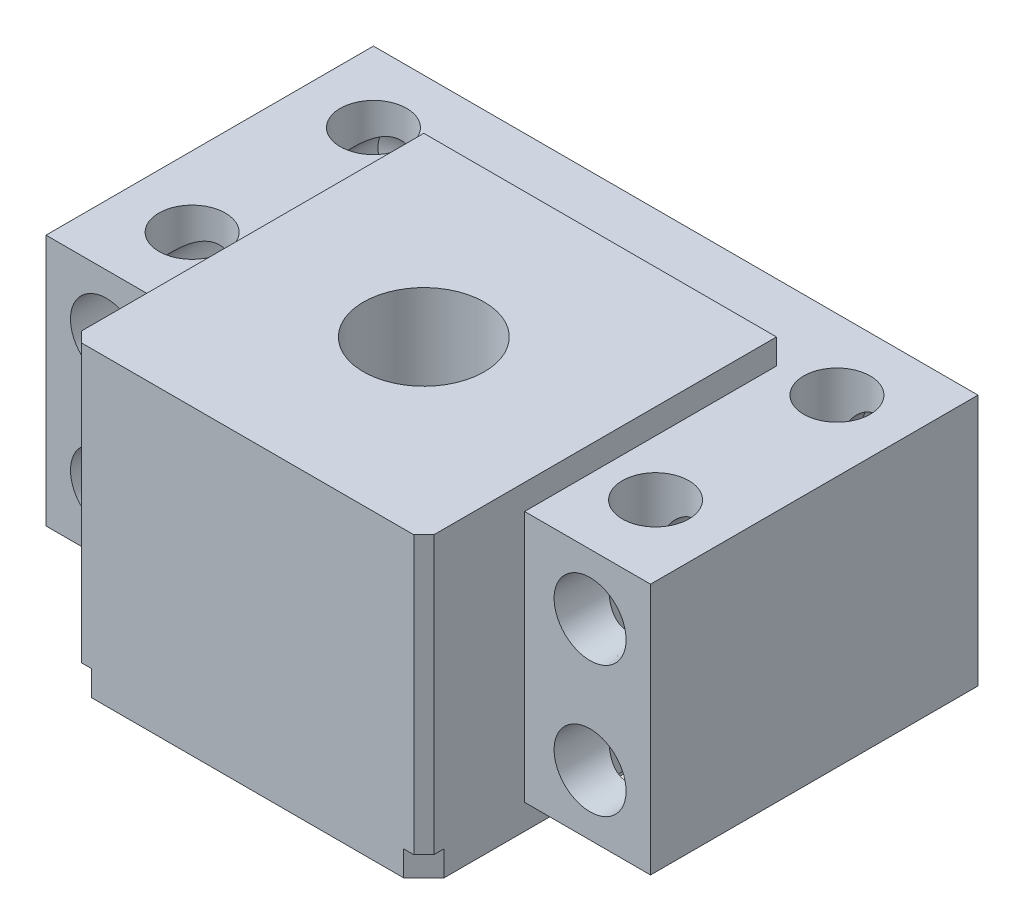
SolidWorks part; units mm, degrees
ref_plane "정면" through (0, 0, 0) normal (0, 0, 1) x (1, 0, 0)
ref_plane "윗면" through (0, 0, 0) normal (0, 1, 0) x (1, 0, 0)
ref_plane "우측면" through (0, 0, 0) normal (1, 0, 0) x (0, 0, -1)
sketch "스케치1" plane through (0, 0, 0) normal (0, 0, 1) x (1, 0, 0)
  line L1 (-30, 12.5) -> (30, 12.5)
  line L2 (-30, 12.5) -> (-30, -12.5)
  line L3 (-30, -12.5) -> (30, -12.5)
  line L4 (30, 12.5) -> (30, -12.5)
  line L5 (-30, 12.5) -> (30, -12.5) construction
  line L6 (-30, -12.5) -> (30, 12.5) construction
  point P0 (0, 0)
  dimension "D1" = 60
  dimension "D2" = 25
extrude "보스-돌출1" add sketch "스케치1" along normal blind 32.5
sketch "스케치2" plane through (0, -12.5, 0) normal (0, -1, 0) x (1, 0, 0)
  line L0 (-30, 0) -> (30, 0) construction
  circle A0 centre (-23, 25) radius 3.3002
  circle A1 centre (-23, 7) radius 3.3
  circle A2 centre (23, 25) radius 3.3002
  circle A3 centre (23, 7) radius 3.3002
  dimension "D1" = 6.6005
  dimension "D2" = 6.6
  dimension "D7" = 6.6005
  dimension "D8" = 6.6005
  dimension "D3" = 18
  dimension "D4" = 25
  dimension "D5" = 25
  dimension "D6" = 18
  dimension "D9" = 23
  dimension "D10" = 0
  dimension "D11" = 46
  dimension "D12" = 46
extrude "컷-돌출1" cut sketch "스케치2" against normal through all contours A1 | A3 | A2 | A0 region at (-23, -12.5, 7) region at (23, -12.5, 25) region at (23, -12.5, 7)
hole_wizard "1/16 Rc 나사 구멍1" positions "스케치3" profile "스케치4" size "1/16" standard "ISO"
sketch "스케치3" plane through (0, 0, 32.5) normal (0, 0, 1) x (1, 0, 0)
  line L0 (30, 12.5) -> (-30, 12.5) construction
  line L1 (-30, 12.5) -> (-30, -12.5) construction
  line L2 (-30, -12.5) -> (30, -12.5) construction
  line L3 (30, -12.5) -> (30, 12.5) construction
  point P0 (-24, 6.5)
  point P2 (-24, -6.5)
  point P4 (24, 6.5)
  point P6 (24, -6.5)
  dimension "D1" = 6
  dimension "D2" = 6
  dimension "D3" = 6
  dimension "D4" = 6
  dimension "D5" = 6
  dimension "D6" = 6
  dimension "D7" = 6
  dimension "D8" = 6
sketch "스케치4" plane through (-24, 6.5, 32.5) normal (1, 0, 0) x (0, -1, 0)
  line L0 (0, 0) -> (0, 31.8326)
  line L1 (3.05, 30) -> (0, 31.8326)
  line L2 (-3.05, 30) -> (0, 31.8326) construction
  line L3 (3.05, 30) -> (3.05, 7.4)
  line L4 (3.05, 7.4) -> (3.34, 7.4)
  line L5 (3.34, 7.4) -> (3.571, 0)
  line L6 (-3.34, 7.4) -> (-3.571, 0) construction
  line L7 (3.571, 0) -> (0, 0)
  line L8 (0, -6.35) -> (0, 107.95) construction
  line L11 (-3.05, 7.4) -> (-3.34, 7.4) construction
  dimension "탭 드릴 지름" = 6.1
  dimension "탭 드릴 깊이" = 30
  dimension "나사산 지름" = 7.142
  dimension "나사산 각도" = 3.576
  dimension "나사산 깊이" = 7.4
  dimension "드릴 각도" = 118
cosmetic thread "구멍 나사산1" parameters "D1"=7.4, "D2"=7.723
cosmetic thread "구멍 나사산2" parameters "D1"=7.4, "D2"=7.723
cosmetic thread "구멍 나사산3" parameters "D1"=7.4, "D2"=7.723
cosmetic thread "구멍 나사산4" parameters "D1"=7.4, "D2"=7.723
sketch "스케치5" plane through (0, -12.5, 0) normal (0, -1, 0) x (1, 0, 0)
  line L0 (-30, 0) -> (30, 0) construction
  line L1 (-17.5, 42.5) -> (17.5, 42.5)
  line L2 (-17.5, 42.5) -> (-17.5, 7.5)
  line L3 (-17.5, 7.5) -> (17.5, 7.5)
  line L4 (17.5, 42.5) -> (17.5, 7.5)
  line L5 (-17.5, 42.5) -> (17.5, 7.5) construction
  line L6 (-17.5, 7.5) -> (17.5, 42.5) construction
  point P0 (0, 25)
  dimension "D1" = 25
  dimension "D2" = 35
  dimension "D3" = 35
extrude "보스-돌출2" add sketch "스케치5" against normal blind 27.5
chamfer "모따기1" distance 1 angle 45 2 edges at (17.5, 1.25, 42.5) (-17.5, 1.25, 42.5)
extrude "보스-돌출3" add sketch "스케치5<2>" along normal blind 2.5
sketch "스케치5<2>" plane through (0, -12.5, 0) normal (0, -1, 0) x (1, 0, 0) same geometry as "스케치5"
chamfer "모따기2" distance 2 angle 45 2 edges at (-17.5, -13.75, 7.5) (17.5, -13.75, 7.5)
sketch "스케치6" plane through (0, -15, 0) normal (0, -1, 0) x (1, 0, 0)
  line L0 (-17.5, 40.5) -> (-15.5, 42.5)
  line L1 (-17.5, 42.5) -> (-17.5, 9.5) construction
  line L2 (17.5, 42.5) -> (-17.5, 42.5) construction
  line L3 (-15.5, 42.5) -> (-17.5, 42.5)
  line L4 (-17.5, 42.5) -> (-17.5, 40.5)
  line L5 (0, 42.5) -> (0, 7.5) construction
  line L6 (-15.5, 7.5) -> (15.5, 7.5) construction
  line L7 (17.5, 42.5) -> (17.5, 40.5)
  line L8 (15.5, 42.5) -> (17.5, 42.5)
  line L9 (17.5, 40.5) -> (15.5, 42.5)
  dimension "D1" = 2
  dimension "D2" = 2
extrude "컷-돌출2" cut sketch "스케치6" against normal up to vertex (2.5 mm away) up to point (-17.5, -12.5, 42.5)
sketch "스케치7" plane through (0, -15, 0) normal (0, -1, 0) x (1, 0, 0)
  line L0 (-15.5, 7.5) -> (15.5, 7.5) construction
  line L1 (-17.5, 32.5) -> (-17.5, 9.5) construction
  circle A0 centre (0, 25) radius 6
  dimension "D3" = 12
  dimension "D1" = 17.5
  dimension "D2" = 17.5
extrude "컷-돌출3" cut sketch "스케치7" against normal through all
equation "\"P\"=6.60047"
equation "\"N\"=17.1778"
